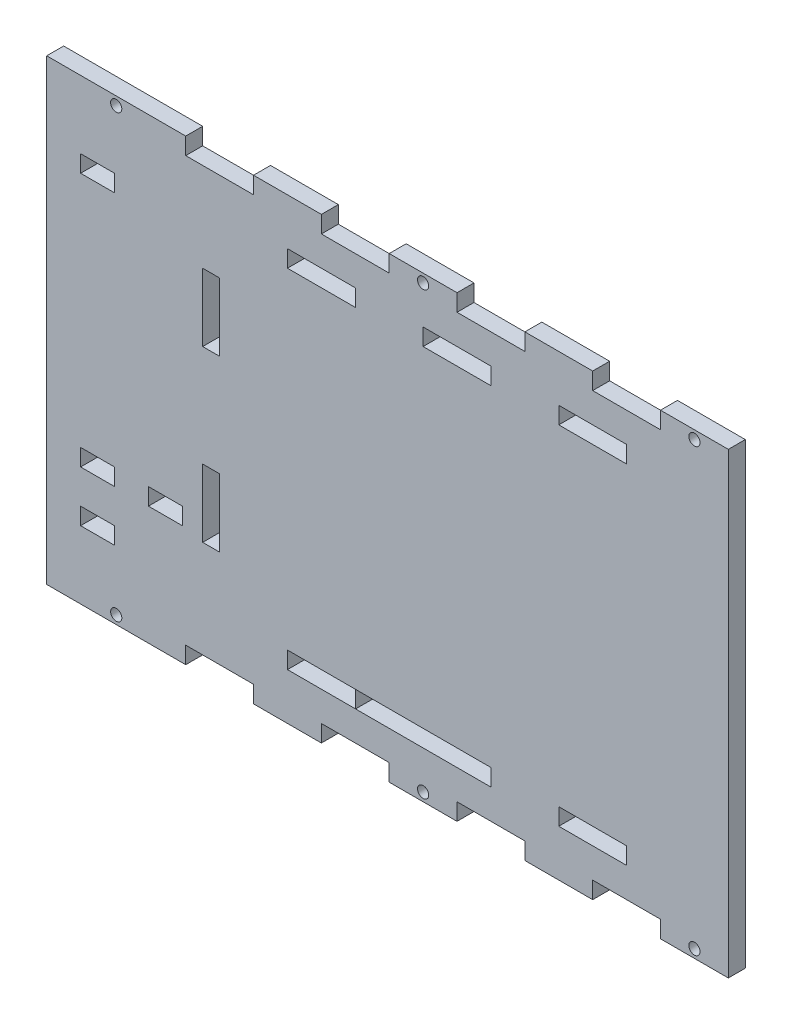
SolidWorks part; units mm, degrees
ref_plane "Front Plane" through (0, 0, 0) normal (0, 0, 1) x (1, 0, 0)
ref_plane "Top Plane" through (0, 0, 0) normal (0, 1, 0) x (1, 0, 0)
ref_plane "Right Plane" through (0, 0, 0) normal (1, 0, 0) x (0, 0, -1)
sketch "Sketch1" plane through (0, 0, 0) normal (0, 0, 1) x (1, 0, 0)
  line L1 (115.91, 155.575) -> (-139.3499, 155.575)
  line L2 (115.91, 155.575) -> (115.91, -15.875)
  line L3 (115.91, -15.875) -> (-139.3499, -15.875)
  line L4 (-139.3499, 155.575) -> (-139.3499, -15.875)
extrude "Boss-Extrude1" add sketch "Sketch1" along normal blind 6.35
sketch "Sketch2" plane through (0, 0, 6.35) normal (0, 0, 1) x (1, 0, 0)
  line L0 (-139.3499, -15.875) -> (115.91, -15.875) construction
  line L1 (-87.29, -9.525) -> (-61.89, -9.525)
  line L2 (-87.29, -9.525) -> (-87.29, -15.875)
  line L3 (-87.29, -15.875) -> (-61.89, -15.875)
  line L4 (-61.89, -9.525) -> (-61.89, -15.875)
  line L5 (-61.89, -9.525) -> (-61.89, -15.875) construction
  line L6 (115.91, 155.575) -> (-139.3499, 155.575) construction
  line L7 (-87.29, 149.225) -> (-61.89, 149.225)
  line L8 (-87.29, 149.225) -> (-87.29, 155.575)
  line L9 (-87.29, 155.575) -> (-61.89, 155.575)
  line L10 (-61.89, 149.225) -> (-61.89, 155.575)
  line L11 (-61.89, 149.225) -> (-61.89, 155.575) construction
extrude "Cut-Extrude1" cut sketch "Sketch2" against normal blind 6.35
pattern_linear "LPattern1" count 4 spacing 50.8 along (1, 0, 0) of "Cut-Extrude1"
sketch "Sketch4" plane through (0, 0, 0) normal (0, 0, -1) x (-1, 0, 0)
  line L0 (115.4535, -9.525) -> (111.1863, -15.875) construction
  line L1 (139.3499, -15.875) -> (87.29, -15.875) construction
  line L2 (111.1863, -9.525) -> (111.1863, -15.875) construction
  line L3 (111.1863, -9.525) -> (115.4535, -15.875) construction
  line L4 (115.4535, -9.525) -> (115.4535, -15.875) construction
  line L5 (-3.7436, -9.525) -> (0.5236, -15.875) construction
  line L6 (11.09, -15.875) -> (-14.31, -15.875) construction
  line L7 (0.5236, -9.525) -> (0.5236, -15.875) construction
  line L8 (0.5236, -9.525) -> (21.5469, -15.875) construction
  line L9 (-101.0764, -9.525) -> (-105.3436, -15.875) construction
  line L10 (-90.51, -15.875) -> (-115.91, -15.875) construction
  line L11 (-105.3436, -9.525) -> (-105.3436, -15.875) construction
  line L12 (-105.3436, -9.525) -> (-75.7859, -15.875) construction
  line L13 (111.1863, 149.225) -> (115.4535, 155.575) construction
  line L14 (87.29, 155.575) -> (139.3499, 155.575) construction
  line L15 (115.4535, 149.225) -> (115.4535, 155.575) construction
  line L16 (115.4535, 149.225) -> (123.8316, 155.575) construction
  line L17 (-3.7436, 149.225) -> (0.5236, 155.575) construction
  line L18 (-14.31, 155.575) -> (11.09, 155.575) construction
  line L19 (0.5236, 149.225) -> (0.5236, 155.575) construction
  line L20 (0.5236, 149.225) -> (-3.7436, 155.575) construction
  line L21 (-101.0764, 149.225) -> (-105.3436, 155.575) construction
  line L22 (-115.91, 155.575) -> (-90.51, 155.575) construction
  line L23 (-105.3436, 149.225) -> (-101.0764, 155.575) construction
  line L24 (-101.0764, 149.225) -> (-101.0764, 155.575) construction
  circle A0 centre (-103.21, -12.7) radius 2.0955
  circle A1 centre (-1.61, -12.7) radius 2.0955
  circle A2 centre (113.3199, -12.7) radius 2.0955
  circle A3 centre (113.3199, 152.4) radius 2.0955
  circle A4 centre (-1.61, 152.4) radius 2.0955
  circle A5 centre (-103.21, 152.4) radius 2.0955
  dimension "D1" = 4.191
extrude "Cut-Extrude2" cut sketch "Sketch4" against normal through all
sketch "Sketch5" plane through (0, 0, 0) normal (0, 0, -1) x (-1, 0, 0)
  line L0 (-27.01, 7.9375) -> (-1.61, 7.9375) construction
  line L1 (-77.81, 1.5875) -> (-52.41, 1.5875)
  line L2 (-77.81, 1.5875) -> (-77.81, 7.9375)
  line L3 (-77.81, 7.9375) -> (-52.41, 7.9375)
  line L4 (-52.41, 1.5875) -> (-52.41, 7.9375)
  line L5 (-27.01, 1.5875) -> (23.6805, 1.5875)
  line L6 (-27.01, 1.5875) -> (-27.01, 7.9375)
  line L7 (-27.01, 7.9375) -> (23.6805, 7.9375)
  line L8 (23.6805, 1.5875) -> (23.6805, 7.9375)
  line L9 (80.94, 90.4875) -> (80.94, 115.8875) construction
  line L10 (23.79, 1.5875) -> (49.19, 1.5875)
  line L11 (23.79, 1.5875) -> (23.79, 7.9375)
  line L12 (23.79, 7.9375) -> (49.19, 7.9375)
  line L13 (49.19, 1.5875) -> (49.19, 7.9375)
  line L14 (74.59, 26.9875) -> (80.94, 26.9875)
  line L15 (74.59, 26.9875) -> (74.59, 52.3875)
  line L16 (74.59, 52.3875) -> (80.94, 52.3875)
  line L17 (80.94, 26.9875) -> (80.94, 52.3875)
  line L18 (74.59, 90.4875) -> (80.94, 90.4875)
  line L19 (74.59, 90.4875) -> (74.59, 115.8875)
  line L20 (74.59, 115.8875) -> (80.94, 115.8875)
  line L21 (80.94, 90.4875) -> (80.94, 115.8875)
  line L22 (80.94, 115.8875) -> (74.59, 115.8875) construction
  line L24 (23.79, 131.7625) -> (49.19, 131.7625)
  line L25 (23.79, 131.7625) -> (23.79, 138.1125)
  line L26 (23.79, 138.1125) -> (49.19, 138.1125)
  line L27 (49.19, 131.7625) -> (49.19, 138.1125)
  line L28 (-27.01, 131.7625) -> (-1.61, 131.7625)
  line L29 (-27.01, 131.7625) -> (-27.01, 138.1125)
  line L30 (-27.01, 138.1125) -> (-1.61, 138.1125)
  line L31 (-1.61, 131.7625) -> (-1.61, 138.1125)
  line L32 (-52.41, 138.1125) -> (-77.81, 138.1125)
  line L33 (-52.41, 138.1125) -> (-52.41, 131.7625)
  line L34 (-52.41, 131.7625) -> (-77.81, 131.7625)
  line L35 (-77.81, 138.1125) -> (-77.81, 131.7625)
extrude "Cut-Extrude3" cut sketch "Sketch5" against normal blind 6.35
sketch "Sketch6" plane through (0, 0, 6.35) normal (0, 0, 1) x (1, 0, 0)
  line L0 (-139.3499, 69.85) -> (-80.94, 69.85) construction
  line L1 (-126.6499, 9.525) -> (-113.9499, 9.525)
  line L2 (-126.6499, 9.525) -> (-126.6499, 15.875)
  line L3 (-126.6499, 15.875) -> (-113.9499, 15.875)
  line L4 (-113.9499, 9.525) -> (-113.9499, 15.875)
  line L5 (-139.3499, 155.575) -> (-139.3499, -15.875) construction
  line L6 (-80.94, 52.3875) -> (-80.94, 90.5062) construction
  line L7 (-113.9499, 130.175) -> (-113.9499, 123.825)
  line L8 (-126.6499, 123.825) -> (-113.9499, 123.825)
  line L9 (-126.6499, 130.175) -> (-126.6499, 123.825)
  line L10 (-126.6499, 130.175) -> (-113.9499, 130.175)
  line L11 (-139.3499, -15.875) -> (-87.29, -15.875) construction
  dimension "D1" = 12.7
  dimension "D2" = 12.7
  dimension "D3" = 6.35
  dimension "D4" = 25.4
extrude "Cut-Extrude4" cut sketch "Sketch6" against normal blind 6.35
sketch "Sketch7" plane through (0, 0, 6.35) normal (0, 0, 1) x (1, 0, 0)
  line L0 (-139.3499, 155.575) -> (-139.3499, -15.875) construction
  line L1 (-126.6499, 34.925) -> (-113.9499, 34.925)
  line L2 (-126.6499, 34.925) -> (-126.6499, 28.575)
  line L3 (-126.6499, 28.575) -> (-113.9499, 28.575)
  line L4 (-113.9499, 34.925) -> (-113.9499, 28.575)
  line L5 (-101.2499, 28.575) -> (-88.5302, 28.575)
  line L6 (-101.2499, 28.575) -> (-101.2499, 34.925)
  line L7 (-101.2499, 34.925) -> (-88.5302, 34.925)
  line L8 (-88.5302, 28.575) -> (-88.5302, 34.925)
  line L9 (-139.3499, -15.875) -> (-87.29, -15.875) construction
  dimension "D1" = 6.35
  dimension "D2" = 6.35
  dimension "D3" = 12.7
  dimension "D4" = 12.7
  dimension "D5" = 12.7
  dimension "D6" = 44.45
  dimension "D7" = 44.45
extrude "Cut-Extrude5" cut sketch "Sketch7" against normal blind 6.35
